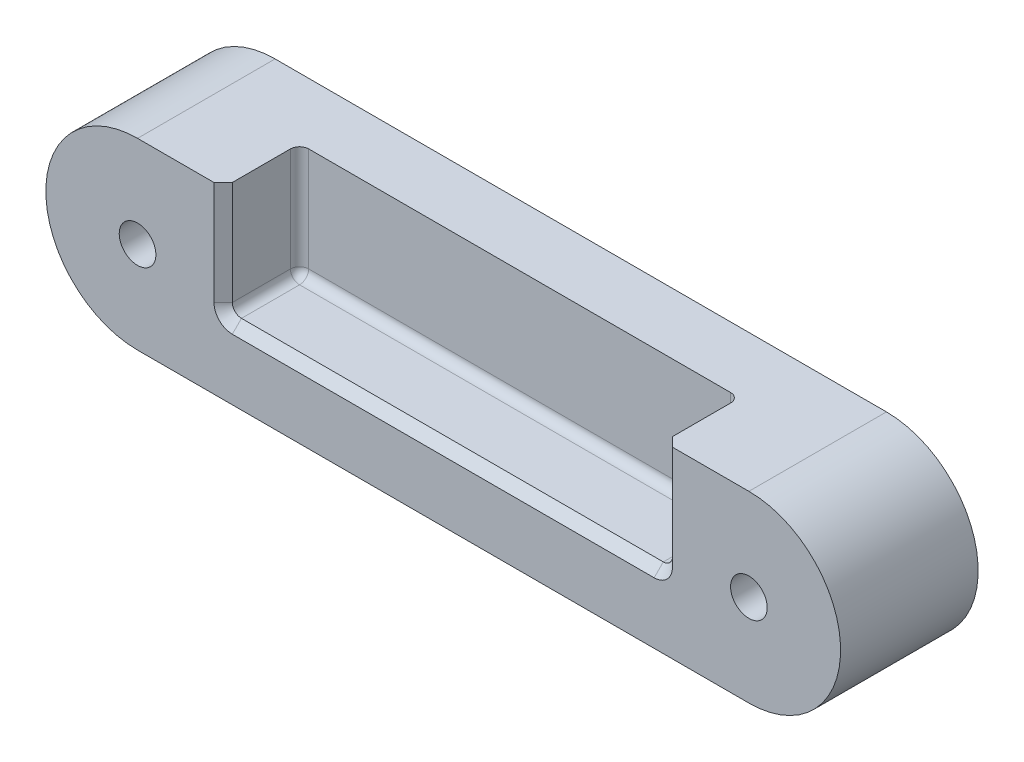
SolidWorks part; units mm, degrees
ref_plane "Front Plane" through (0, 0, 0) normal (0, 0, 1) x (1, 0, 0)
ref_plane "Top Plane" through (0, 0, 0) normal (0, 1, 0) x (1, 0, 0)
ref_plane "Right Plane" through (0, 0, 0) normal (1, 0, 0) x (0, 0, -1)
sketch "Sketch1" plane through (0, 0, 0) normal (0, 0, 1) x (1, 0, 0)
  line L0 (-100, 0) -> (100, 0) construction
  line L1 (-100, 30) -> (100, 30)
  line L2 (-100, -30) -> (100, -30)
  arc A0 (-100, 30) -> (-100, -30) centre (-100, 0) ccw
  arc A1 (100, -30) -> (100, 30) centre (100, 0) ccw
  circle A2 centre (-100, 0) radius 6
  circle A3 centre (100, 0) radius 6
  point P3 (0, 0)
  dimension "D1" = 30
  dimension "D3" = 12
  dimension "D2" = 200
extrude "Boss-Extrude1" add sketch "Sketch1" along normal blind 45
sketch "Sketch2" plane through (0, 0, 45) normal (0, 0, 1) x (1, 0, 0)
  line L0 (100, 30) -> (-100, 30) construction
  line L1 (-72, -7) -> (72, -7)
  line L2 (-72, -7) -> (-72, 30)
  line L3 (-72, 30) -> (72, 30)
  line L4 (72, -7) -> (72, 30)
  line L5 (-72, -7) -> (72, 30) construction
  line L6 (-72, 30) -> (72, -7) construction
  line L7 (0, 11.5) -> (0, 0) construction
  point P0 (0, 11.5)
  point P10 (0, 15.1623)
  dimension "D1" = 144
  dimension "D2" = 37
extrude "Cut-Extrude1" cut sketch "Sketch2" against normal blind 25
fillet "Fillet1" radius 3 5 edges at (72, 11.5, 20) (0, -7, 20) (-72, 11.5, 20) (72, -7, 32.5) (-72, -7, 32.5)
chamfer "Chamfer1" distance 3 angle 45 5 edges at (72, 13, 45) (0, -7, 45) (-72, 13, 45) (71.1213, -6.1213, 45) (-71.1213, -6.1213, 45)
